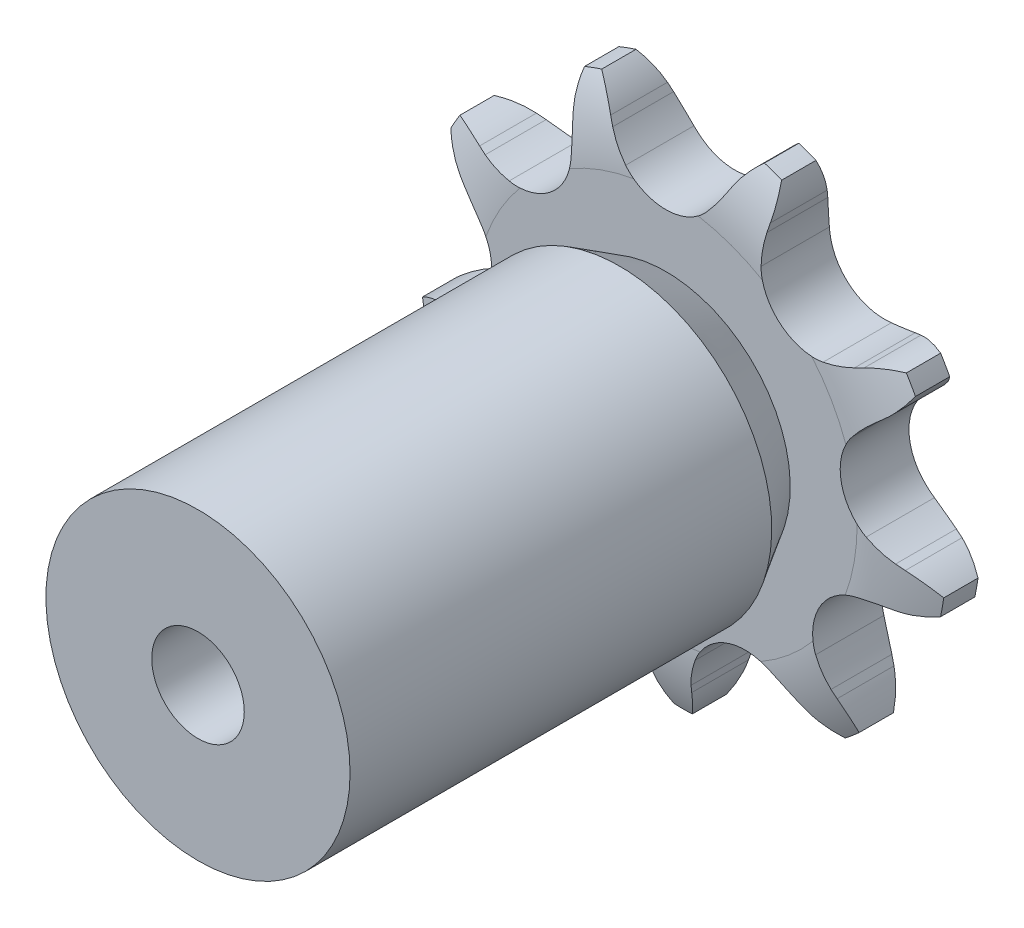
SolidWorks part; units mm, degrees
ref_plane "Front Plane" through (0, 0, 0) normal (0, 0, 1) x (1, 0, 0)
ref_plane "Top Plane" through (0, 0, 0) normal (0, 1, 0) x (1, 0, 0)
ref_plane "Right Plane" through (0, 0, 0) normal (1, 0, 0) x (0, 0, -1)
sketch "Sketch0" plane through (0, 0, 0) normal (0, 0, 1) x (1, 0, 0)
  line L0 (3, -8.2424) -> (0, 0) construction
  line L1 (0, 0) -> (7.5963, -4.3857) construction
  line L2 (0, 0) -> (-3, -8.2424) construction
  line L3 (3, -8.2424) -> (7.5963, -4.3857) construction
  line L4 (3, -8.2424) -> (-3, -8.2424) construction
  line L5 (5.0985, -7.2441) -> (4.8625, -7.0453)
  line L6 (3, -8.2424) -> (0, -9.3343) construction
  line L7 (0.7508, -8.8266) -> (0.8038, -8.5226)
  line L8 (0, -8.2424) -> (0, -10.0424) construction
  line L9 (3.972, -6.4397) -> (1.4813, -11.0591) construction
  line L10 (0, 0) -> (0, -8.2424) construction
  line L11 (4.8625, -7.0453) -> (1.4813, -11.0591) construction
  line L12 (0, -10.0424) -> (0, -10.4354) construction
  line L13 (7.2898, -4.6428) -> (5.0985, -7.2441) construction
  circle A0 centre (0, 0) radius 10.0424 construction
  circle A1 centre (0, 0) radius 8.7714 construction
  arc A2 (-3.6232, -11.4862) -> (10.1587, -6.47) centre (0, 0) ccw
  circle A3 centre (0, 0) radius 10.4354 construction
  circle A4 centre (3, -8.2424) radius 2 construction
  arc A7 (3.972, -6.4397) -> (1.0966, -7.4863) centre (3, -8.2424) ccw
  circle A8 centre (3, -8.2424) radius 2.0481 construction
  arc A9 (5.0985, -7.2441) -> (10.1587, -6.47) centre (7.2898, -4.6428) ccw
  arc A10 (4.8625, -7.0453) -> (3.972, -6.4397) centre (1.4813, -11.0591) ccw
  arc A11 (0.7508, -8.8266) -> (-3.6232, -11.4862) centre (-2.6, -8.2424) cw
  arc A12 (0.8038, -8.5226) -> (1.0966, -7.4863) centre (5.9739, -9.4239) cw
  dimension "D1" = 2.0481
  dimension "R" = 2.0481
sketch "Sketch1" plane through (0, 0, 0) normal (1, 0, 0) x (0, 0, -1)
  line L0 (1.3, 0) -> (-1.3, 0)
  line L1 (-1.3, 0) -> (-1.3, 7.23)
  line L2 (-1.3, 8.7714) -> (0, 8.7714) construction
  line L3 (-0.6, 10.0424) -> (0.6, 10.0424)
  line L5 (1.3, 7.23) -> (1.3, 0)
  line L7 (0, 10.0424) -> (0, 0) construction
  line L8 (-1.3, 7.23) -> (1.3, 7.23) construction
  line L9 (0, 10.0424) -> (0, -10.0424) construction
  line L10 (-1.3, 7.23) -> (-1.3, 10.0424) construction
  line L11 (-1.3, 10.0424) -> (-0.6, 10.0424) construction
  line L12 (0.6, 10.0424) -> (1.3, 10.0424) construction
  line L13 (1.3, 10.0424) -> (1.3, 7.23) construction
  line L14 (0, 0) -> (-6.4008, 0) construction
  line L15 (-1.3, 8.7714) -> (-1.3, 4.6714) construction
  line L22 (1.3, 0) -> (-8.7, 0) construction
  line L24 (-1.3, 0) -> (-1.3, 4.6714) construction
  arc A0 (-0.6, 10.0424) -> (-1.3, 7.23) centre (4.7, 7.23) ccw
  arc A1 (0.6, 10.0424) -> (1.3, 7.23) centre (-4.7, 7.23) cw
  dimension "R" = 6
revolve "Revolve1" add sketch "Sketch1" angle 360 mid plane about L0
extrude "Cut-Extrude1" cut sketch "Sketch0" against normal through all and the other way through all
pattern_circular "CirPattern1" count 9 over 360 about axis through (0, 0, -1.3) along (0, 0, -1) of "Cut-Extrude1"
sketch "Sketch2" plane through (0, 0, 0) normal (0, 0, 1) x (1, 0, 0)
  circle A0 centre (0, 0) radius 2.5 construction
  circle A1 centre (0, 0) radius 5.75
  circle A2 centre (0, 0) radius 9.95 construction
  dimension "Bore" = 5
  dimension "Hub Dia." = 11.5
  dimension "OD" = 19.9
extrude "Boss-Extrude1" add sketch "Sketch2" along normal up to vertex (8.7 mm away) from surface up to point (0, 0, 8.7) starting at face at (0, 0, 1.3)
sketch "Sketch3" plane through (0, 0, 0) normal (0, 0, 1) x (1, 0, 0)
  circle A0 centre (0, 0) radius 2.5 construction
  circle A1 centre (0, 0) radius 2.5
extrude "Cut-Extrude2" cut sketch "Sketch3" along normal through all and the other way through all
sketch "Sketch4" plane through (0, 0, 0) normal (1, 0, 0) x (0, 0, -1)
  line L0 (-8.7, 5.75) -> (-8.7, 5.25)
  line L1 (-1.3, 10.0424) -> (-3.25, 10.0424)
  line L2 (-1.3, 10.0424) -> (-1.3, 4.6714)
  line L3 (-1.3, 4.6714) -> (-3.25, 4.6714)
  line L4 (-3.25, 10.0424) -> (-3.25, 4.6714)
  line L9 (-8.7, 5.25) -> (-8.2, 5.75)
  line L10 (-8.2, 5.75) -> (-8.7, 5.75)
  dimension "C" = 0.5
  dimension "D3" = 1.95
revolve "Cut-Revolve1" cut sketch "Sketch4" angle 360 mid plane about L22
sketch "Sketch5" plane through (0, 0, 0) normal (0, 0, 1) x (1, 0, 0)
  circle A0 centre (0, 0) radius 9.95 construction
  circle A1 centre (0, 0) radius 9.95
extrude "Cut-Extrude3" cut sketch "Sketch5" against normal through all and the other way through all flip side to cut
ref_plane "Plane1" through (0, 0, 8.2) normal (0, 0, 1) x (1, 0, 0)
sketch "Sketch6" plane through (0, 0, 8.2) normal (0, 0, 1) x (1, 0, 0)
  circle A0 centre (0, 0) radius 5.75
  circle A1 centre (0, 0) radius 2.5
  dimension "D1" = 11.5
  dimension "D2" = 5
extrude "Boss-Extrude2" add sketch "Sketch6" along normal blind 10.79
sketch "Sketch7" plane through (0, 0, 0) normal (0, 0, 1) x (1, 0, 0)
  circle A0 centre (0, 0) radius 2.5
  circle A1 centre (0, 0) radius 1.75
  dimension "D1" = 5
  dimension "D2" = 3.5
extrude "Boss-Extrude3" add sketch "Sketch7" along normal up to surface (18.99 mm away) and the other way up to surface (1.3 mm away) up to face at (5.75, 0, 18.99) other way up to face at (0, 0, -1.3)
chamfer "Chamfer1" distance 1.2 distance2 2 1 edges at (0, 4.6714, 3.25) first distance on face at (0, 4.6714, 3.25)
equation "\"360/N@Sketch0\" = 360/\"Teeth@CirPattern1\""
equation "\"Ds@Sketch0\" = 1.005 * \"Dr@Sketch0\" + ( 0.003 * 25.4 ) "
equation "\"R@Sketch0\" = 1/2 * \"Ds@Sketch0\""
equation "\"A@Sketch0\" = 35 +  ( 60 / \"Teeth@CirPattern1\" ) "
equation "\"B@Sketch0\" = 18 -  ( 56 / \"Teeth@CirPattern1\" )"
equation "\"ac@Sketch0\" = 0.8 * \"Dr@Sketch0\""
equation "\"ab@Sketch0\" = 1.4 * \"Dr@Sketch0\""
equation "\"J@Sketch0\" = 0.3 * \"Pitch@Sketch0\""
equation "\"D3@Sketch4\" = \"t@Sketch1\" * 3 / 4"
